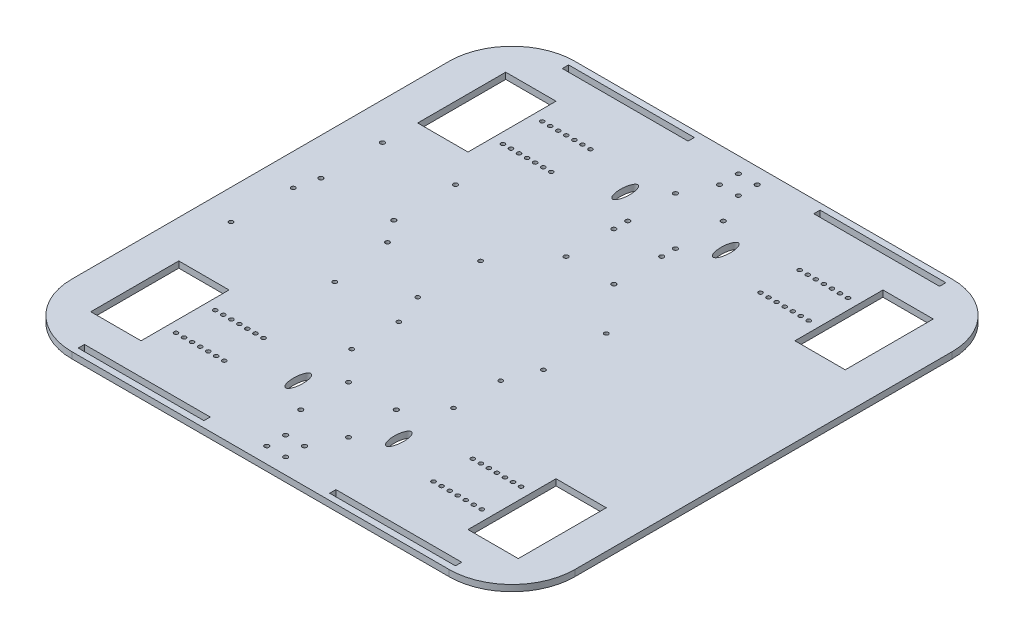
SolidWorks part; units mm, degrees
ref_plane "Front Plane" through (0, 0, 0) normal (0, 0, 1) x (1, 0, 0)
ref_plane "Top Plane" through (0, 0, 0) normal (0, 1, 0) x (1, 0, 0)
ref_plane "Right Plane" through (0, 0, 0) normal (1, 0, 0) x (0, 0, -1)
sketch "Sketch1" plane through (0, 0, 0) normal (0, 1, 0) x (1, 0, 0)
  line L0 (0, -1000) -> (0, 49000) construction
  line L1 (-170, 165) -> (-130, 165)
  line L2 (-170, 165) -> (-170, 95)
  line L3 (-170, 95) -> (-130, 95)
  line L4 (-130, 165) -> (-130, 95)
  line L5 (170, 95) -> (130, 95)
  line L6 (130, 165) -> (130, 95)
  line L7 (170, 165) -> (130, 165)
  line L8 (170, 165) -> (170, 95)
  line L9 (-1000, 0) -> (49000, 0) construction
  line L10 (-10, 190) -> (10, 190)
  line L11 (-10, 190) -> (-10, 170)
  line L12 (-10, 170) -> (10, 170)
  line L13 (10, 190) -> (10, 170)
  line L14 (-1010, 180) -> (48990, 180) construction
  line L15 (-1010, -180) -> (48990, -180) construction
  line L16 (0, 1000) -> (0, -49000) construction
  line L17 (-10, -170) -> (10, -170)
  line L18 (10, -190) -> (10, -170)
  line L19 (-10, -190) -> (10, -190)
  line L20 (-10, -190) -> (-10, -170)
  line L21 (170, -165) -> (170, -95)
  line L22 (-200, 200) -> (200, 200)
  line L23 (-200, 200) -> (-200, -200)
  line L24 (-200, -200) -> (200, -200)
  line L25 (200, 200) -> (200, -200)
  line L26 (170, -165) -> (130, -165)
  line L27 (130, -165) -> (130, -95)
  line L28 (170, -95) -> (130, -95)
  line L29 (-170, -95) -> (-130, -95)
  line L30 (-130, -165) -> (-130, -95)
  line L31 (-170, -165) -> (-130, -165)
  line L32 (-170, -165) -> (-170, -95)
  circle A0 centre (0, 0) radius 200 construction
  circle A1 centre (-7.5, 187.5) radius 1.75
  circle A2 centre (7.5, 187.5) radius 1.75
  circle A3 centre (7.5, 172.5) radius 1.75
  circle A4 centre (-7.5, 172.5) radius 1.75
  circle A5 centre (7.5, -187.5) radius 1.75
  circle A6 centre (-7.5, -187.5) radius 1.75
  circle A7 centre (-7.5, -172.5) radius 1.75
  circle A8 centre (7.5, -172.5) radius 1.75
  point P8 (-150, 165)
  point P19 (0, 190)
  point P22 (-10, 180)
  dimension "D1" = 400
  dimension "D7" = 3.5
  dimension "D2" = 40
  dimension "D3" = 70
  dimension "D4" = 150
  dimension "D5" = 20
  dimension "D6" = 180
  dimension "D8" = 2.5
  dimension "D9" = 2.5
  dimension "D10" = 35
extrude "Boss-Extrude2" add sketch "Sketch1" along normal blind 5 contours L25 L22 L23 L24 L1 L4 L3 L2 L7 L8 L5 L6 L10 L13 L12 L11 L19 L20 L17 L18 | L20 L19 L18 L17 A6 A5 A7 A8 | L13 L10 L11 L12 A2 A1 A3 A4 region at (0, 0, -180) region at (0, 0, 180) region at (0, 0, 0)
fillet "Fillet1" radius 50 4 edges at (200, 2.5, -200) (200, 2.5, 200) (-200, 2.5, 200) (-200, 2.5, -200)
sketch "Sketch2" plane through (0, 5, 0) normal (0, 1, 0) x (1, 0, 0)
  line L0 (-1094.0419, 130) -> (48905.9581, 130) construction
  line L1 (-130, 148.8) -> (-78.5, 148.8) construction
  line L2 (-130, 148.8) -> (-130, 111.2) construction
  line L3 (-130, 111.2) -> (-78.5, 111.2) construction
  line L4 (-78.5, 148.8) -> (-78.5, 111.2) construction
  line L5 (-130, 165) -> (-130, 95) construction
  line L6 (-170, 165) -> (-170, 95) construction
  line L7 (0, -1000) -> (0, 49000) construction
  line L8 (130, 111.2) -> (78.5, 111.2) construction
  line L9 (78.5, 148.8) -> (78.5, 111.2) construction
  line L10 (130, 148.8) -> (78.5, 148.8) construction
  line L11 (130, 148.8) -> (130, 111.2) construction
  line L12 (-1000, 0) -> (49000, 0) construction
  line L13 (130, -148.8) -> (130, -111.2) construction
  line L14 (130, -148.8) -> (78.5, -148.8) construction
  line L15 (78.5, -148.8) -> (78.5, -111.2) construction
  line L16 (130, -111.2) -> (78.5, -111.2) construction
  line L17 (-78.5, -148.8) -> (-78.5, -111.2) construction
  line L18 (-130, -111.2) -> (-78.5, -111.2) construction
  line L19 (-130, -148.8) -> (-130, -111.2) construction
  line L20 (-130, -148.8) -> (-78.5, -148.8) construction
  line L21 (-1094.0419, -130) -> (48905.9581, -130) construction
  circle A0 centre (-121.6, 145.6) radius 1.6
  circle A1 centre (-115.2, 145.6) radius 1.6
  circle A2 centre (-108.8, 145.6) radius 1.6
  circle A3 centre (-102.4, 145.6) radius 1.6
  circle A4 centre (-96, 145.6) radius 1.6
  circle A5 centre (-89.6, 145.6) radius 1.6
  circle A6 centre (-83.2, 145.6) radius 1.6
  circle A7 centre (-83.2, 114.4) radius 1.6
  circle A8 centre (-89.6, 114.4) radius 1.6
  circle A9 centre (-96, 114.4) radius 1.6
  circle A10 centre (-102.4, 114.4) radius 1.6
  circle A11 centre (-108.8, 114.4) radius 1.6
  circle A12 centre (-115.2, 114.4) radius 1.6
  circle A13 centre (-121.6, 114.4) radius 1.6
  circle A14 centre (83.2, 114.4) radius 1.6
  circle A15 centre (89.6, 114.4) radius 1.6
  circle A16 centre (96, 114.4) radius 1.6
  circle A17 centre (102.4, 114.4) radius 1.6
  circle A18 centre (108.8, 114.4) radius 1.6
  circle A19 centre (115.2, 114.4) radius 1.6
  circle A20 centre (121.6, 114.4) radius 1.6
  circle A21 centre (83.2, 145.6) radius 1.6
  circle A22 centre (89.6, 145.6) radius 1.6
  circle A23 centre (96, 145.6) radius 1.6
  circle A24 centre (102.4, 145.6) radius 1.6
  circle A25 centre (108.8, 145.6) radius 1.6
  circle A26 centre (115.2, 145.6) radius 1.6
  circle A27 centre (121.6, 145.6) radius 1.6
  circle A28 centre (121.6, -145.6) radius 1.6
  circle A29 centre (115.2, -145.6) radius 1.6
  circle A30 centre (108.8, -145.6) radius 1.6
  circle A31 centre (102.4, -145.6) radius 1.6
  circle A32 centre (96, -145.6) radius 1.6
  circle A33 centre (89.6, -145.6) radius 1.6
  circle A34 centre (83.2, -145.6) radius 1.6
  circle A35 centre (121.6, -114.4) radius 1.6
  circle A36 centre (115.2, -114.4) radius 1.6
  circle A37 centre (108.8, -114.4) radius 1.6
  circle A38 centre (102.4, -114.4) radius 1.6
  circle A39 centre (96, -114.4) radius 1.6
  circle A40 centre (89.6, -114.4) radius 1.6
  circle A41 centre (83.2, -114.4) radius 1.6
  circle A42 centre (-121.6, -114.4) radius 1.6
  circle A43 centre (-115.2, -114.4) radius 1.6
  circle A44 centre (-108.8, -114.4) radius 1.6
  circle A45 centre (-102.4, -114.4) radius 1.6
  circle A46 centre (-96, -114.4) radius 1.6
  circle A47 centre (-89.6, -114.4) radius 1.6
  circle A48 centre (-83.2, -114.4) radius 1.6
  circle A49 centre (-83.2, -145.6) radius 1.6
  circle A50 centre (-89.6, -145.6) radius 1.6
  circle A51 centre (-96, -145.6) radius 1.6
  circle A52 centre (-102.4, -145.6) radius 1.6
  circle A53 centre (-108.8, -145.6) radius 1.6
  circle A54 centre (-115.2, -145.6) radius 1.6
  circle A55 centre (-121.6, -145.6) radius 1.6
  point P9 (-130, 130)
  point P40 (-170, 130)
  dimension "D3" = 3.2
  dimension "D7" = 6.4
  dimension "D5" = 8.4
  dimension "D1" = 37.6
  dimension "D2" = 4.7
  dimension "D4" = 31.2
  dimension "D6" = 7
extrude "Cut-Extrude1" cut sketch "Sketch2" against normal blind 5
sketch "Sketch3" plane through (0, 5, 0) normal (0, 1, 0) x (1, 0, 0)
  line L0 (-150, -200) -> (150, -200) construction
  line L1 (-190, 3.34) -> (-88.4, 3.34) construction
  line L2 (-190, 3.34) -> (-190, -50) construction
  line L3 (-190, -50) -> (-88.4, -50) construction
  line L4 (-88.4, 3.34) -> (-88.4, -50) construction
  line L5 (-200, 150) -> (-200, -150) construction
  circle A0 centre (-176.03, -47.46) radius 1.65
  circle A1 centre (-174.76, 0.8) radius 1.65
  circle A2 centre (-93.48, -47.46) radius 1.65
  circle A3 centre (-99.83, 0.8) radius 1.65
  dimension "D5" = 3.3
  dimension "D8" = 3.3
  dimension "D9" = 96.52
  dimension "D10" = 90.17
  dimension "D1" = 101.6
  dimension "D2" = 53.34
  dimension "D3" = 13.97
  dimension "D4" = 2.54
  dimension "D6" = 15.24
  dimension "D7" = 50.8
  dimension "D11" = 150
  dimension "D12" = 10
extrude "Cut-Extrude2" cut sketch "Sketch3" against normal blind 10 contours A1 | A2 | L2 L1 L4 L3 | A0 | A3 region at (-174.76, 5, -0.8) region at (-93.48, 5, 47.46)
sketch "Sketch4" plane through (0, 5, 0) normal (0, 1, 0) x (1, 0, 0)
  line L0 (-19, 149) -> (19, 149) construction
  line L1 (-1149.7342, 130) -> (48850.2658, 130) construction
  line L2 (-22, 152) -> (22, 152) construction
  line L3 (-22, 152) -> (-22, 108) construction
  line L4 (-22, 108) -> (22, 108) construction
  line L5 (22, 152) -> (22, 108) construction
  line L6 (-19, 111) -> (19, 111) construction
  line L7 (-19, 100) -> (19, 100) construction
  line L8 (-1231.3219, 81) -> (48768.6781, 81) construction
  line L9 (-22, 103) -> (22, 103) construction
  line L10 (-22, 103) -> (-22, 59) construction
  line L11 (-22, 59) -> (22, 59) construction
  line L12 (22, 103) -> (22, 59) construction
  line L13 (-19, 62) -> (19, 62) construction
  line L14 (-19, -149) -> (19, -149) construction
  line L15 (-22, -152) -> (22, -152) construction
  line L16 (-130, 165) -> (-130, 95) construction
  line L17 (-150, 200) -> (150, 200) construction
  line L18 (22, -108) -> (22, -152) construction
  line L19 (-22, -108) -> (-22, -152) construction
  line L20 (-19, -111) -> (19, -111) construction
  line L21 (-22, -108) -> (22, -108) construction
  line L22 (-1022, -130) -> (48978, -130) construction
  line L23 (-130, -165) -> (-130, -95) construction
  circle A0 centre (-19, 149) radius 1.75
  circle A1 centre (19, 149) radius 1.75
  circle A2 centre (19, 111) radius 1.75
  circle A3 centre (-19, 111) radius 1.75
  circle A4 centre (-19, 100) radius 1.75
  circle A5 centre (19, 100) radius 1.75
  circle A6 centre (19, 62) radius 1.75
  circle A7 centre (-19, 62) radius 1.75
  circle A8 centre (-19, -149) radius 1.75
  circle A9 centre (19, -149) radius 1.75
  circle A10 centre (-19, -111) radius 1.75
  circle A11 centre (19, -111) radius 1.75
  point P9 (0, 149)
  point P10 (0, 152)
  point P14 (-22, 130)
  point P26 (0, 100)
  point P27 (0, 103)
  point P31 (-22, 81)
  point P38 (-130, 130)
  point P39 (0, 200)
  point P40 (0, 108)
  point P56 (-22, -130)
  point P58 (-130, -130)
  dimension "D1" = 3.5
  dimension "D5" = 3.5
  dimension "D2" = 38
  dimension "D3" = 44
  dimension "D4" = 38
  dimension "D6" = 38
  dimension "D7" = 44
  dimension "D8" = 38
  dimension "D9" = 5
  dimension "D10" = 2
extrude "Cut-Extrude3" cut sketch "Sketch4" against normal blind 10
sketch "Sketch5" plane through (0, 5, 0) normal (0, 1, 0) x (1, 0, 0)
  line L0 (-1136.3236, 43) -> (48863.6764, 43) construction
  line L1 (-174, 15) -> (-89, 15) construction
  line L2 (-174, 15) -> (-174, 71) construction
  line L3 (-174, 71) -> (-89, 71) construction
  line L4 (-89, 15) -> (-89, 71) construction
  line L5 (-180, 10) -> (-83, 10) construction
  line L6 (-180, 10) -> (-180, 76) construction
  line L7 (-180, 76) -> (-83, 76) construction
  line L8 (-83, 10) -> (-83, 76) construction
  line L9 (-200, 150) -> (-200, -150) construction
  line L10 (-150, -200) -> (150, -200) construction
  circle A0 centre (-170.5, 67.5) radius 1.75
  circle A1 centre (-112.5, 67.5) radius 1.75
  circle A2 centre (-112.5, 18.5) radius 1.75
  circle A3 centre (-170.5, 18.5) radius 1.75
  dimension "D4" = 3.5
  dimension "D5" = 3.5
  dimension "D1" = 56
  dimension "D2" = 85
  dimension "D3" = 58
  dimension "D6" = 3.5
  dimension "D7" = 49
  dimension "D8" = 3.5
  dimension "D9" = 5
  dimension "D10" = 5
  dimension "D11" = 6
  dimension "D12" = 6
  dimension "D13" = 20
  dimension "D14" = 210
extrude "Cut-Extrude4" cut sketch "Sketch5" against normal blind 10
sketch "Sketch6" plane through (0, 5, 0) normal (0, 1, 0) x (1, 0, 0)
  line L0 (-130, 165) -> (-130, 95) construction
  line L1 (0, -800) -> (0, 49200) construction
  line L2 (-150, 200) -> (150, 200) construction
  line L3 (-1200, 0) -> (48800, 0) construction
  line L4 (-200, 150) -> (-200, -150) construction
  ellipse E0 centre (-40, 130) end of major axis (-40, 140) minor radius 3.75
  ellipse E1 centre (40, 130) end of major axis (40, 140) minor radius 3.75
  ellipse E2 centre (40, -130) end of major axis (40, -140) minor radius 3.75
  ellipse E3 centre (-40, -130) end of major axis (-40, -140) minor radius 3.75
  point P13 (-130, 130)
  point P14 (-200, 0)
  point P26 (0, 200)
  dimension "D1" = 90
  dimension "D2" = 20
  dimension "D3" = 7.5
extrude "Cut-Extrude5" cut sketch "Sketch6" against normal blind 10
sketch "Sketch7" plane through (0, 5, 0) normal (0, 1, 0) x (1, 0, 0)
  line L0 (0, -1008.1082) -> (0, 48991.8918) construction
  line L1 (-53, 28) -> (53, 28) construction
  line L2 (-53, 28) -> (-53, -28) construction
  line L3 (-53, -28) -> (53, -28) construction
  line L4 (53, 28) -> (53, -28) construction
  line L5 (-53, 28) -> (-47, 28) construction
  line L6 (-53, 28) -> (-53, 22) construction
  line L7 (-53, 22) -> (-47, 22) construction
  line L8 (-47, 28) -> (-47, 22) construction
  line L9 (-1053, 0) -> (48947, 0) construction
  line L10 (-150, -200) -> (150, -200) construction
  line L11 (-200, 150) -> (-200, -150) construction
  circle A1 centre (-50, 25) radius 1.65
  circle A2 centre (50, 25) radius 1.65
  circle A3 centre (50, -25) radius 1.65
  circle A4 centre (-50, -25) radius 1.65
  point P10 (-50, 22)
  point P15 (-47, 25)
  point P16 (0, 28)
  point P17 (-53, 0)
  point P25 (0, -200)
  point P28 (-200, 0)
  dimension "D3" = 3.3
  dimension "D1" = 106
  dimension "D2" = 56
  dimension "D5" = 6
  dimension "D6" = 6
extrude "Cut-Extrude6" cut sketch "Sketch7" against normal blind 10
sketch "Sketch8" plane through (0, 5, 0) normal (0, 1, 0) x (1, 0, 0)
  line L0 (0, -1046.6714) -> (0, 48953.3286) construction
  line L1 (-43.5, -46.5) -> (43.5, -46.5) construction
  line L2 (-43.5, -46.5) -> (-43.5, -90) construction
  line L3 (-43.5, -90) -> (43.5, -90) construction
  line L4 (43.5, -46.5) -> (43.5, -90) construction
  line L5 (-43.5, -46.5) -> (-37.5, -46.5) construction
  line L6 (-43.5, -46.5) -> (-43.5, -52.5) construction
  line L7 (-43.5, -52.5) -> (-37.5, -52.5) construction
  line L8 (-37.5, -46.5) -> (-37.5, -52.5) construction
  line L9 (-1043.5, -68.25) -> (48956.5, -68.25) construction
  line L10 (37.5, -46.5) -> (37.5, -52.5) construction
  line L11 (43.5, -52.5) -> (37.5, -52.5) construction
  line L12 (-150, -200) -> (150, -200) construction
  circle A0 centre (-40.5, -49.5) radius 1.65
  circle A1 centre (40.5, -49.5) radius 1.65
  circle A2 centre (40.5, -87) radius 1.65
  circle A3 centre (-40.5, -87) radius 1.65
  point P10 (-40.5, -52.5)
  point P11 (-37.5, -49.5)
  point P15 (0, -46.5)
  point P17 (-43.5, -68.25)
  point P28 (0, -200)
  dimension "D3" = 3.3
  dimension "D1" = 87
  dimension "D2" = 6
  dimension "D4" = 43.5
  dimension "D5" = 110
extrude "Cut-Extrude7" cut sketch "Sketch8" against normal blind 5
sketch "Sketch9" plane through (0, 5, 0) normal (0, 1, 0) x (1, 0, 0)
  line L0 (-150, 200) -> (150, 200) construction
  line L1 (-150, 195) -> (-50, 195)
  line L2 (-150, 195) -> (-150, 190)
  line L3 (-150, 190) -> (-50, 190)
  line L4 (-50, 195) -> (-50, 190)
  line L5 (0, -800) -> (0, 49200) construction
  line L6 (150, 190) -> (50, 190)
  line L7 (50, 195) -> (50, 190)
  line L8 (150, 195) -> (50, 195)
  line L9 (150, 195) -> (150, 190)
  line L10 (-1200, 0) -> (48800, 0) construction
  line L11 (-200, 150) -> (-200, -150) construction
  line L12 (150, -195) -> (150, -190)
  line L13 (150, -195) -> (50, -195)
  line L14 (50, -195) -> (50, -190)
  line L15 (150, -190) -> (50, -190)
  line L16 (-150, -190) -> (-50, -190)
  line L17 (-50, -195) -> (-50, -190)
  line L18 (-150, -195) -> (-50, -195)
  line L19 (-150, -195) -> (-150, -190)
  point P13 (0, 200)
  point P22 (-200, 0)
  dimension "D1" = 5
  dimension "D2" = 5
  dimension "D3" = 100
extrude "Cut-Extrude8" cut sketch "Sketch9" against normal blind 10
